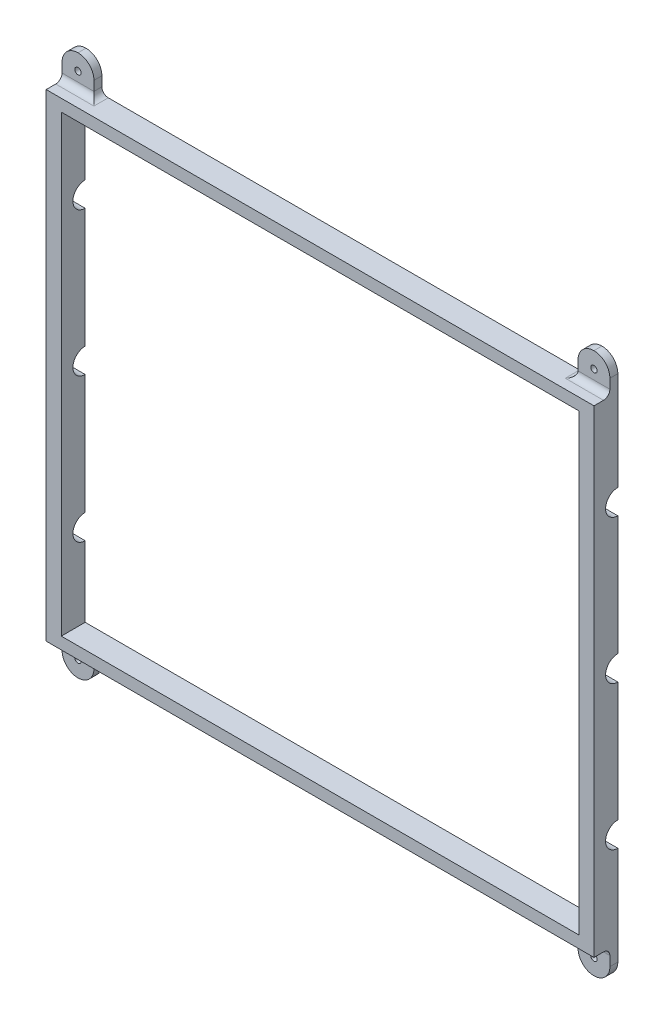
SolidWorks part; units mm, degrees
ref_plane "Front Plane" through (0, 0, 0) normal (0, 0, 1) x (1, 0, 0)
ref_plane "Top Plane" through (0, 0, 0) normal (0, 1, 0) x (1, 0, 0)
ref_plane "Right Plane" through (0, 0, 0) normal (1, 0, 0) x (0, 0, -1)
sketch "Sketch1" plane through (0, 0, 0) normal (0, 0, 1) x (1, 0, 0)
  line L1 (-109.22, -95.25) -> (109.22, -95.25)
  line L2 (-109.22, -95.25) -> (-109.22, 95.25)
  line L3 (-109.22, 95.25) -> (109.22, 95.25)
  line L4 (109.22, -95.25) -> (109.22, 95.25)
  line L5 (-109.22, -95.25) -> (109.22, 95.25) construction
  line L6 (-109.22, 95.25) -> (109.22, -95.25) construction
  point P0 (0, 0)
  dimension "D1" = 218.44
  dimension "D2" = 190.5
extrude "Boss-Extrude1" add sketch "Sketch1" along normal blind 9.525
sketch "Sketch2" plane through (0, 0, 9.525) normal (0, 0, 1) x (1, 0, 0)
  line L1 (-103.1875, -90.4875) -> (103.1875, -90.4875)
  line L2 (-103.1875, -90.4875) -> (-103.1875, 90.4875)
  line L3 (-103.1875, 90.4875) -> (103.1875, 90.4875)
  line L4 (103.1875, -90.4875) -> (103.1875, 90.4875)
  line L5 (-103.1875, -90.4875) -> (103.1875, 90.4875) construction
  line L6 (-103.1875, 90.4875) -> (103.1875, -90.4875) construction
  point P0 (0, 0)
  dimension "D1" = 206.375
  dimension "D2" = 180.975
extrude "Cut-Extrude1" cut sketch "Sketch2" against normal blind 9.525
sketch "Sketch3" plane through (109.22, 0, 0) normal (1, 0, 0) x (0, 0, -1)
  line L0 (0, -95.25) -> (0, 95.25) construction
  circle A0 centre (0, 0) radius 4.8895
  circle A1 centre (0, 57.404) radius 4.8895
  circle A2 centre (0, -57.404) radius 4.8895
  dimension "D1" = 9.779
  dimension "D2" = 9.779
  dimension "D3" = 9.779
  dimension "D4" = 57.404
  dimension "D5" = 57.404
extrude "Cut-Extrude2" cut sketch "Sketch3" against normal through all
sketch "Sketch4" plane through (0, 0, 0) normal (0, 0, -1) x (-1, 0, 0)
  line L1 (-109.22, 95.25) -> (-96.52, 95.25)
  line L2 (-109.22, 95.25) -> (-109.22, 107.95)
  line L3 (-109.22, 107.95) -> (-96.52, 107.95)
  line L4 (-96.52, 95.25) -> (-96.52, 107.95)
  dimension "D1" = 12.7
  dimension "D2" = 12.7
extrude "Boss-Extrude2" add sketch "Sketch4" against normal blind 3.175
sketch "Sketch5" plane through (0, 0, 3.175) normal (0, 0, 1) x (1, 0, 0)
  line L0 (96.52, 101.6) -> (109.22, 101.6) construction
  line L3 (102.87, 107.95) -> (102.87, 95.25) construction
  line L6 (109.22, 107.95) -> (109.22, 95.25) construction
  line L7 (96.52, 107.95) -> (109.22, 107.95) construction
  circle A0 centre (102.87, 101.6) radius 1.27
  dimension "D4" = 2.54
  dimension "D1" = 6.35
  dimension "D2" = 6.35
  dimension "D3" = 6.35
extrude "Cut-Extrude3" cut sketch "Sketch5" against normal through all
fillet "Fillet1" radius 6.35 2 edges at (96.52, 107.95, 1.5875) (109.22, 107.95, 1.5875)
fillet "Fillet2" radius 2.54 2 edges at (96.52, 95.25, 1.5875) (102.87, 95.25, 3.175)
mirror "Mirror1" about plane through (0, 0, 0) normal (1, 0, 0) of "Boss-Extrude2", "Cut-Extrude3", "Fillet1", "Fillet2"
sketch "Sketch6" plane through (0, 0, 0) normal (0, 0, -1) x (-1, 0, 0)
  line L1 (-109.22, -95.25) -> (-96.52, -95.25)
  line L2 (-109.22, -95.25) -> (-109.22, -107.95)
  line L3 (-109.22, -107.95) -> (-96.52, -107.95)
  line L4 (-96.52, -95.25) -> (-96.52, -107.95)
  circle A0 centre (-102.87, -101.6) radius 1.27
  dimension "D5" = 2.54
  dimension "D1" = 12.7
  dimension "D2" = 12.7
  dimension "D3" = 6.35
  dimension "D4" = 6.35
extrude "Boss-Extrude3" add sketch "Sketch6" against normal blind 3.175
fillet "Fillet3" radius 2.54 2 edges at (96.52, -95.25, 1.5875) (102.87, -95.25, 3.175)
fillet "Fillet4" radius 6.35 2 edges at (109.22, -107.95, 1.5875) (96.52, -107.95, 1.5875)
mirror "Mirror7" about plane through (0, 0, 0) normal (1, 0, 0) of "Fillet4", "Fillet3", "Boss-Extrude3"
